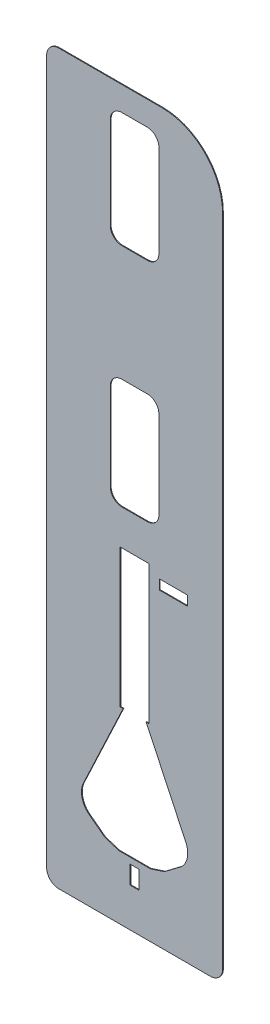
SolidWorks part; units mm, degrees
material "Melinex 454"
ref_plane "Front Plane" through (0, 0, 0) normal (0, 0, 1) x (1, 0, 0)
ref_plane "Top Plane" through (0, 0, 0) normal (0, 1, 0) x (1, 0, 0)
ref_plane "Right Plane" through (0, 0, 0) normal (1, 0, 0) x (0, 0, -1)
sketch "Sketch8" plane through (0, 0, 0) normal (0, 0, 1) x (1, 0, 0)
  line L0 (0, 60) -> (0, -60) construction
  line L1 (-12.5, 60) -> (4.5, 60)
  line L2 (-14.5, 58) -> (-14.5, -58)
  line L3 (-12.5, -60) -> (12.5, -60)
  line L4 (14.5, 50) -> (14.5, -58)
  line L5 (-14.5, 60) -> (14.5, -60) construction
  line L6 (-14.5, -60) -> (14.5, 60) construction
  line L7 (-14.5, 0) -> (14.5, 0) construction
  line L8 (0, -55) -> (0, 55) construction
  arc A0 (-14.5, -58) -> (-12.5, -60) centre (-12.5, -58) ccw
  arc A1 (12.5, -60) -> (14.5, -58) centre (12.5, -58) ccw
  arc A2 (4.5, 60) -> (14.5, 50) centre (4.5, 50) cw
  arc A3 (-12.5, 60) -> (-14.5, 58) centre (-12.5, 58) ccw
  point P0 (0, 0)
extrude "Boss-Extrude5" add sketch "Sketch8" along normal blind 0.125 separate body
sketch "Sketch1" plane through (0, 0, 0.125) normal (0, 0, 1) x (1, 0, 0)
  line L124 (-4.925, -48.85) -> (-2.6, -49.6) construction
  line L165 (2.1, 56) -> (-2.1, 56) construction
  line L167 (4, 38.9) -> (4, 54.1) construction
  line L186 (-2.1, 37) -> (2.1, 37) construction
  line L187 (-4, 54.1) -> (-4, 38.9) construction
  line L188 (2.1, 17.9318) -> (-2.1, 17.9318) construction
  line L190 (4, 1.6) -> (4, 16.0318) construction
  line L194 (-2.1, -0.3) -> (2.1, -0.3) construction
  line L202 (-4, 16.0318) -> (-4, 1.6) construction
  line L205 (2.4, -6.15) -> (-2.4, -6.15) construction
  line L206 (2.4, -29) -> (2.4, -6.15) construction
  line L213 (-2.4, -6.15) -> (-2.4, -29) construction
  line L222 (8.74, -7.47) -> (4.08, -7.47) construction
  line L225 (4.08, -7.47) -> (4.08, -9.07) construction
  line L230 (4.08, -9.07) -> (8.74, -9.07) construction
  line L231 (8.74, -9.07) -> (8.74, -7.47) construction
  line L232 (-2.4, -29) -> (-1.9, -29) construction
  line L233 (1.9, -29) -> (2.4, -29) construction
  line L234 (8.375, -42.75) -> (1.9, -29) construction
  line L235 (-1.9, -29) -> (-8.375, -42.75) construction
  line L236 (-7.4, -46.9731) -> (-4.925, -48.85) construction
  line L237 (-2.6, -49.6) -> (2.6, -49.6) construction
  line L238 (0.75, -50.6) -> (-0.75, -50.6) construction
  line L239 (0.75, -53.6) -> (0.75, -50.6) construction
  line L240 (-0.75, -53.6) -> (0.75, -53.6) construction
  line L241 (-0.75, -50.6) -> (-0.75, -53.6) construction
  line L242 (2.6, -49.6) -> (4.925, -48.85) construction
  line L243 (4.925, -48.85) -> (7.4, -46.9731) construction
  line L244 (4.925, -48.85) -> (7.4, -46.9731)
  line L245 (2.6, -49.6) -> (4.925, -48.85)
  line L246 (-0.75, -50.6) -> (-0.75, -53.6)
  line L247 (-0.75, -53.6) -> (0.75, -53.6)
  line L248 (0.75, -53.6) -> (0.75, -50.6)
  line L249 (0.75, -50.6) -> (-0.75, -50.6)
  line L250 (-2.6, -49.6) -> (2.6, -49.6)
  line L251 (-4.925, -48.85) -> (-2.6, -49.6)
  line L252 (-7.4, -46.9731) -> (-4.925, -48.85)
  line L253 (-1.9, -29) -> (-8.375, -42.75)
  line L254 (8.375, -42.75) -> (1.9, -29)
  line L255 (1.9, -29) -> (2.4, -29)
  line L256 (-2.4, -29) -> (-1.9, -29)
  line L257 (8.74, -9.07) -> (8.74, -7.47)
  line L258 (4.08, -9.07) -> (8.74, -9.07)
  line L259 (4.08, -7.47) -> (4.08, -9.07)
  line L260 (8.74, -7.47) -> (4.08, -7.47)
  line L261 (-2.4, -6.15) -> (-2.4, -29)
  line L262 (2.4, -29) -> (2.4, -6.15)
  line L263 (2.4, -6.15) -> (-2.4, -6.15)
  line L264 (-4, 16.0318) -> (-4, 1.6)
  line L265 (-2.1, -0.3) -> (2.1, -0.3)
  line L266 (4, 1.6) -> (4, 16.0318)
  line L267 (2.1, 17.9318) -> (-2.1, 17.9318)
  line L268 (-4, 54.1) -> (-4, 38.9)
  line L269 (-2.1, 37) -> (2.1, 37)
  line L270 (4, 38.9) -> (4, 54.1)
  line L271 (2.1, 56) -> (-2.1, 56)
  arc A124 (-2.1, 56) -> (-4, 54.1) centre (-2.1, 54.1) ccw construction
  arc A133 (4, 54.1) -> (2.1, 56) centre (2.1, 54.1) ccw construction
  arc A150 (2.1, 37) -> (4, 38.9) centre (2.1, 38.9) ccw construction
  arc A151 (-4, 38.9) -> (-2.1, 37) centre (-2.1, 38.9) ccw construction
  arc A152 (4, 16.0318) -> (2.1, 17.9318) centre (2.1, 16.0318) ccw construction
  arc A153 (2.1, -0.3) -> (4, 1.6) centre (2.1, 1.6) ccw construction
  arc A154 (-4, 1.6) -> (-2.1, -0.3) centre (-2.1, 1.6) ccw construction
  arc A155 (-2.1, 17.9318) -> (-4, 16.0318) centre (-2.1, 16.0318) ccw construction
  arc A156 (-2.1, 17.9318) -> (-4, 16.0318) centre (-2.1, 16.0318) ccw
  arc A157 (-4, 1.6) -> (-2.1, -0.3) centre (-2.1, 1.6) ccw
  arc A158 (2.1, -0.3) -> (4, 1.6) centre (2.1, 1.6) ccw
  arc A159 (4, 16.0318) -> (2.1, 17.9318) centre (2.1, 16.0318) ccw
  arc A160 (-4, 38.9) -> (-2.1, 37) centre (-2.1, 38.9) ccw
  arc A161 (2.1, 37) -> (4, 38.9) centre (2.1, 38.9) ccw
  arc A162 (4, 54.1) -> (2.1, 56) centre (2.1, 54.1) ccw
  arc A163 (-2.1, 56) -> (-4, 54.1) centre (-2.1, 54.1) ccw
  spline S0 degree 3 poles (-1836.1355, -3592.7026) (2222.5014, 3309.4868) (-2600.2291, -3121.4243) (2902.6094, 2687.0541) knots -40.180202 -40.180202 -40.180202 -40.180202 44.080876 44.080876 44.080876 44.080876 only from (-8.375, -42.75) to (-8.75, -44.3) construction
  spline S1 degree 3 poles (3156.3673, -2476.859) (-2885.9846, 2765.5821) (2531.5071, -3169.0107) (-2157.875, 3316.9521) knots -17.902772 -17.902772 -17.902772 -17.902772 25.226336 25.226336 25.226336 25.226336 only from (-8.75, -44.3) to (-7.4, -46.9731) construction
  spline S2 degree 3 poles (2157.885, 3316.966) (-2531.5149, -3169.0192) (2885.9891, 2765.586) (-3156.3676, -2476.8592) knots -18.228062 -18.228062 -18.228062 -18.228062 24.901077 24.901077 24.901077 24.901077 only from (7.4, -46.9731) to (8.75, -44.3) construction
  spline S3 degree 3 poles (-2902.6247, 2687.0702) (2600.2145, -3121.4114) (-2222.4639, 3309.4382) (1836.0834, -3592.6141) knots -39.080954 -39.080954 -39.080954 -39.080954 45.179842 45.179842 45.179842 45.179842 only from (8.75, -44.3) to (8.375, -42.75) construction
  spline S4 degree 3 poles (8.75, -44.3) (8.7497, -43.7369) (8.614, -43.206) (8.375, -42.75) knots 2 2 2 2 3 3 3 3
  spline S5 degree 3 poles (7.4, -46.9731) (8.2114, -46.4163) (8.7506, -45.4277) (8.75, -44.3) knots 3 3 3 3 3.998305 3.998305 3.998305 3.998305
  spline S6 degree 3 poles (-8.75, -44.3) (-8.7506, -45.4277) (-8.2114, -46.4163) (-7.4, -46.9731) knots 3 3 3 3 3.998305 3.998305 3.998305 3.998305
  spline S7 degree 3 poles (-8.375, -42.75) (-8.614, -43.206) (-8.7497, -43.7369) (-8.75, -44.3) knots 2 2 2 2 3 3 3 3
extrude "Cut-Extrude2" cut sketch "Sketch1" against normal through all contours L271 A163 L268 A160 L269 A161 L270 A162 | L266 A159 L267 A156 L264 A157 L265 A158 | L253 S7 S6 L252 L251 L250 L245 L244 S5 S4 L254 L255 L262 L263 L261 L256 | L246 L247 L248 L249 | L258 L257 L260 L259 region at (0, -33.5633, 0.125) region at (0, 8.8159, 0.125) region at (0, 46.5, 0.125)
